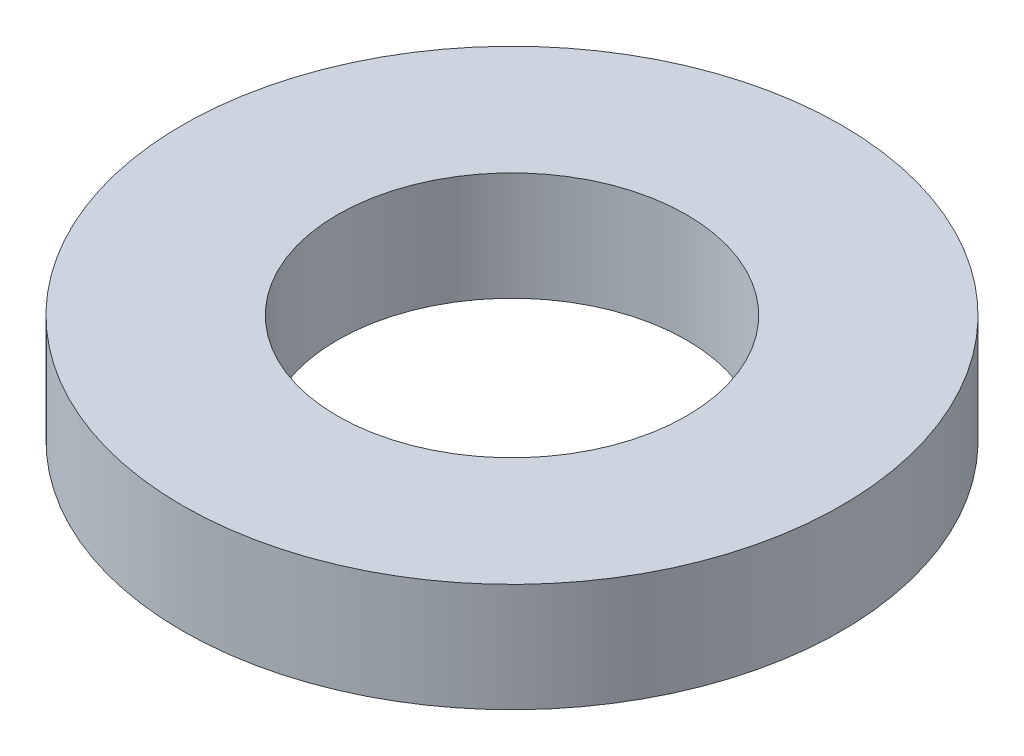
SolidWorks part; units mm, degrees
ref_plane "Front Plane" through (0, 0, 0) normal (0, 0, 1) x (1, 0, 0)
ref_plane "Top Plane" through (0, 0, 0) normal (0, 1, 0) x (1, 0, 0)
ref_plane "Right Plane" through (0, 0, 0) normal (1, 0, 0) x (0, 0, -1)
sketch "Sketch1" plane through (0, 0, 0) normal (0, 1, 0) x (1, 0, 0)
  circle A0 centre (0, 0) radius 85
  dimension "FLANGE_OD" = 170
extrude "Boss-Extrude1" add sketch "Sketch1" along normal blind 28
sketch "Sketch2" plane through (0, 0, 0) normal (0, 1, 0) x (1, 0, 0)
  circle A0 centre (0, 0) radius 45
  dimension "BORE_D" = 90
extrude "Cut-Extrude1" cut sketch "Sketch2" along normal through all
sketch "Sketch3" plane through (0, 28, 0) normal (0, 1, 0) x (1, 0, 0)
  circle A0 centre (0, 0) radius 28.3715 construction
  circle A1 centre (-28.3715, 0) radius 2.8968
  dimension "BOLT_D" = 5.7937
  dimension "BOLT_PCD" = 56.7429
extrude "Cut-Extrude2" cut sketch "Sketch3" against normal blind 25.9176 rebuild error yes
pattern_circular "CirPattern1" count 5 over 360 rebuild error yes
